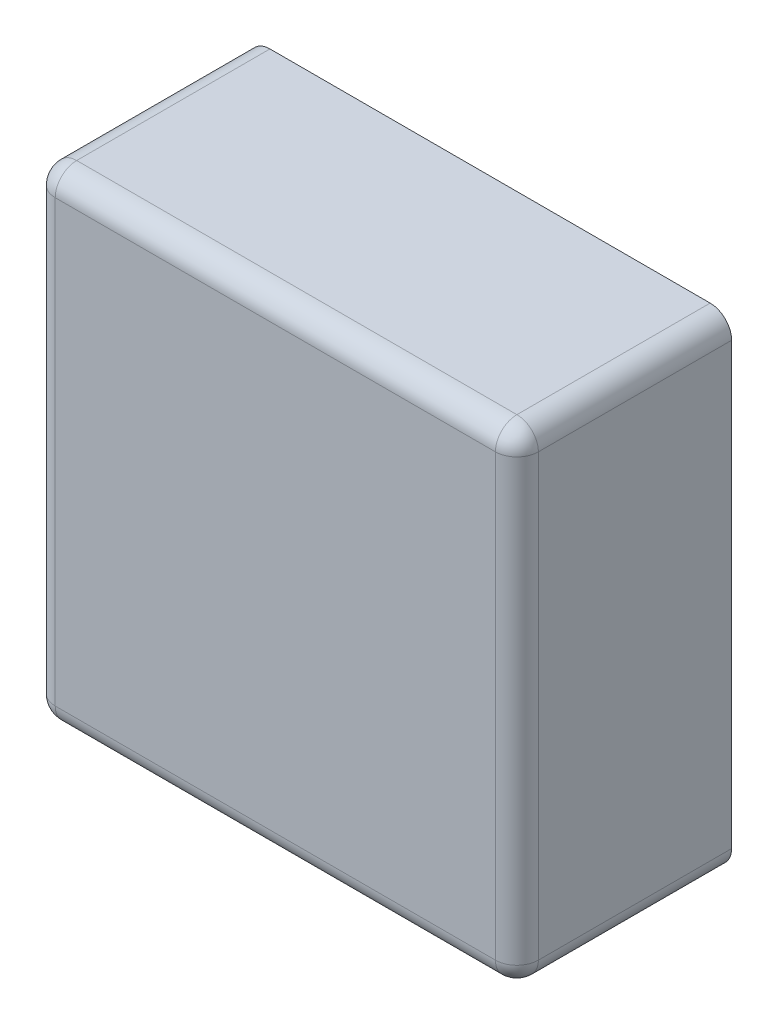
SolidWorks part; units mm, degrees
ref_plane "Piano frontale" through (0, 0, 0) normal (0, 0, 1) x (1, 0, 0)
ref_plane "Piano superiore" through (0, 0, 0) normal (0, 1, 0) x (1, 0, 0)
ref_plane "Piano destro" through (0, 0, 0) normal (1, 0, 0) x (0, 0, -1)
sketch "Schizzo1" plane through (0, 0, 0) normal (0, 0, 1) x (1, 0, 0)
  line L1 (0, 0) -> (45, 0)
  line L2 (0, 0) -> (0, 45)
  line L3 (0, 45) -> (45, 45)
  line L4 (45, 0) -> (45, 45)
  dimension "D1" = 45
  dimension "D2" = 45
  dimension "D3" = 45
  dimension "D4" = 45
extrude "Estrusione-Estrusione1" add sketch "Schizzo1" along normal blind 20
shell "Svuota2" thickness 2 removed face at (22.5, 22.5, 0)
sketch "Schizzo3" plane through (0, 0, 0) normal (0, -1, 0) x (-1, 0, 0)
  line L1 (-34.6883, -17.9455) -> (-41.1883, -17.9455)
  line L2 (-34.6883, -17.9455) -> (-34.6883, -14.1455)
  line L3 (-34.6883, -14.1455) -> (-41.1883, -14.1455)
  line L4 (-41.1883, -17.9455) -> (-41.1883, -14.1455)
  dimension "D1" = 6.5
  dimension "D2" = 3.8
extrude "Taglio-Estrusione1" cut sketch "Schizzo3" against normal blind 2
sketch "Schizzo4" plane through (0, 0, 0) normal (0, -1, 0) x (1, 0, 0)
  line L1 (6.117, 16.4219) -> (23.5848, 16.4219)
  line L2 (6.117, 16.4219) -> (6.117, 10.7114)
  line L3 (6.117, 10.7114) -> (23.5848, 10.7114)
  line L4 (23.5848, 16.4219) -> (23.5848, 10.7114)
extrude "Taglio-Estrusione2" cut sketch "Schizzo4" against normal blind 3
sketch "Schizzo8" plane through (0, 0, 0) normal (0, -1, 0) x (1, 0, 0)
  line L1 (27.8183, 7.521) -> (38.3183, 7.521)
  line L2 (27.8183, 7.521) -> (27.8183, 5.521)
  line L3 (27.8183, 5.521) -> (38.3183, 5.521)
  line L4 (38.3183, 7.521) -> (38.3183, 5.521)
  dimension "D1" = 10.5
  dimension "D2" = 2
extrude "Taglio-Estrusione3" cut sketch "Schizzo8" against normal blind 3
fillet "Raccordo3" radius 2 7 edges at (22.5, 0, 20) (45, 22.5, 20) (0, 0, 10) (0, 22.5, 20) (45, 45, 10) (22.5, 45, 20) (0, 45, 10) tangent propagation no
fillet "Raccordo4" radius 2 2 edges at (44.4142, 0.5858, 19.4142) (45, 0, 9)
fillet "Raccordo5" radius 0.5 4 edges at (2, 2, 9) (43, 2, 9) (2, 43, 9) (43, 43, 9)
